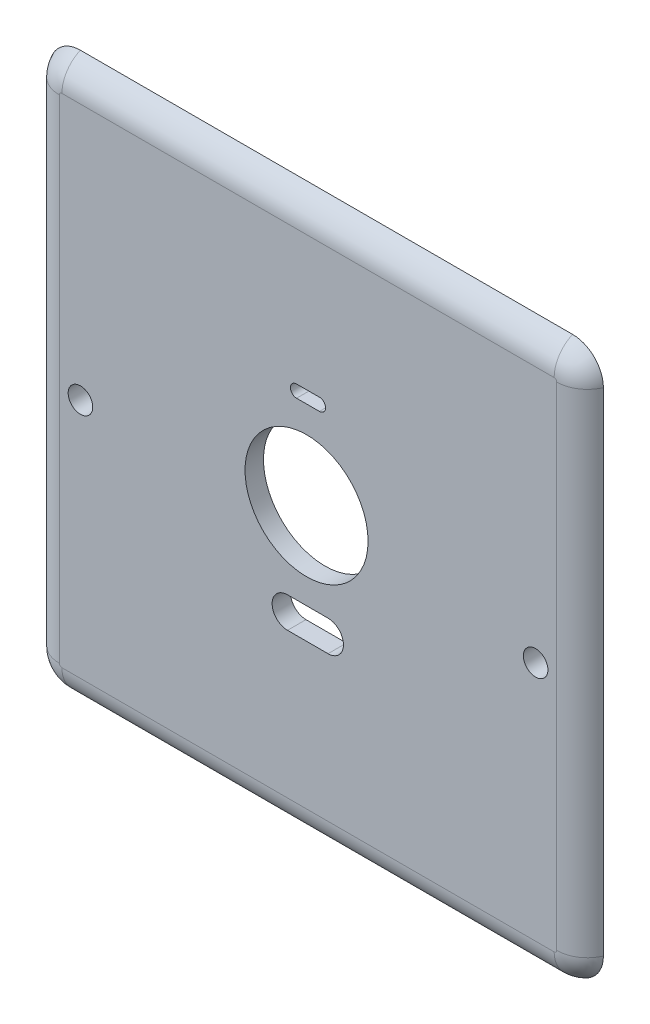
SolidWorks part; units mm, degrees
ref_plane "Front Plane" through (0, 0, 0) normal (0, 0, 1) x (1, 0, 0)
ref_plane "Top Plane" through (0, 0, 0) normal (0, 1, 0) x (1, 0, 0)
ref_plane "Right Plane" through (0, 0, 0) normal (1, 0, 0) x (0, 0, -1)
sketch "Sketch1" plane through (0, 0, 0) normal (0, 0, 1) x (1, 0, 0)
  line L1 (-96.25, 27.1875) -> (-6.25, 27.1875)
  line L2 (-96.25, 27.1875) -> (-96.25, -62.8125)
  line L3 (-96.25, -62.8125) -> (-6.25, -62.8125)
  line L4 (-6.25, 27.1875) -> (-6.25, -62.8125)
  dimension "D1" = 90
  dimension "D2" = 90
extrude "Boss-Extrude1" add sketch "Sketch1" along normal blind 3
fillet "Fillet1" radius 5 4 edges at (-96.25, 27.1875, 1.5) (-6.25, 27.1875, 1.5) (-6.25, -62.8125, 1.5) (-96.25, -62.8125, 1.5)
fillet "Fillet3" radius 5 8 edges at (-94.7855, 25.723, 3) (-51.25, 27.1875, 3) (-7.7145, 25.723, 3) (-6.25, -17.8125, 3) (-7.7145, -61.348, 3) (-51.25, -62.8125, 3) (-94.7855, -61.348, 3) (-96.25, -17.8125, 3)
sketch "Sketch2" plane through (0, 0, 3) normal (0, 0, 1) x (1, 0, 0)
  line L0 (-54.5835, -32.1286) -> (-47.9966, -32.1286) construction
  line L1 (-54.5835, -29.6286) -> (-47.9966, -29.6286)
  line L2 (-54.5835, -34.6286) -> (-47.9966, -34.6286)
  line L3 (-53.1136, -0.2287) -> (-49.3975, -0.2287) construction
  line L4 (-53.1136, 0.7713) -> (-49.3975, 0.7713)
  line L5 (-53.1136, -1.2287) -> (-49.3975, -1.2287)
  circle A0 centre (-51.492, -15.545) radius 10
  arc A1 (-54.5835, -29.6286) -> (-54.5835, -34.6286) centre (-54.5835, -32.1286) ccw
  arc A2 (-47.9966, -34.6286) -> (-47.9966, -29.6286) centre (-47.9966, -32.1286) ccw
  arc A3 (-53.1136, 0.7713) -> (-53.1136, -1.2287) centre (-53.1136, -0.2287) ccw
  arc A4 (-49.3975, -1.2287) -> (-49.3975, 0.7713) centre (-49.3975, -0.2287) ccw
  circle A5 centre (-88.2384, -19.0513) radius 2
  circle A6 centre (-14.2616, -19.0513) radius 2
  point P4 (-51.2901, -32.1286)
  point P11 (-51.2555, -0.2287)
extrude "Cut-Extrude1" cut sketch "Sketch2" against normal blind 3
